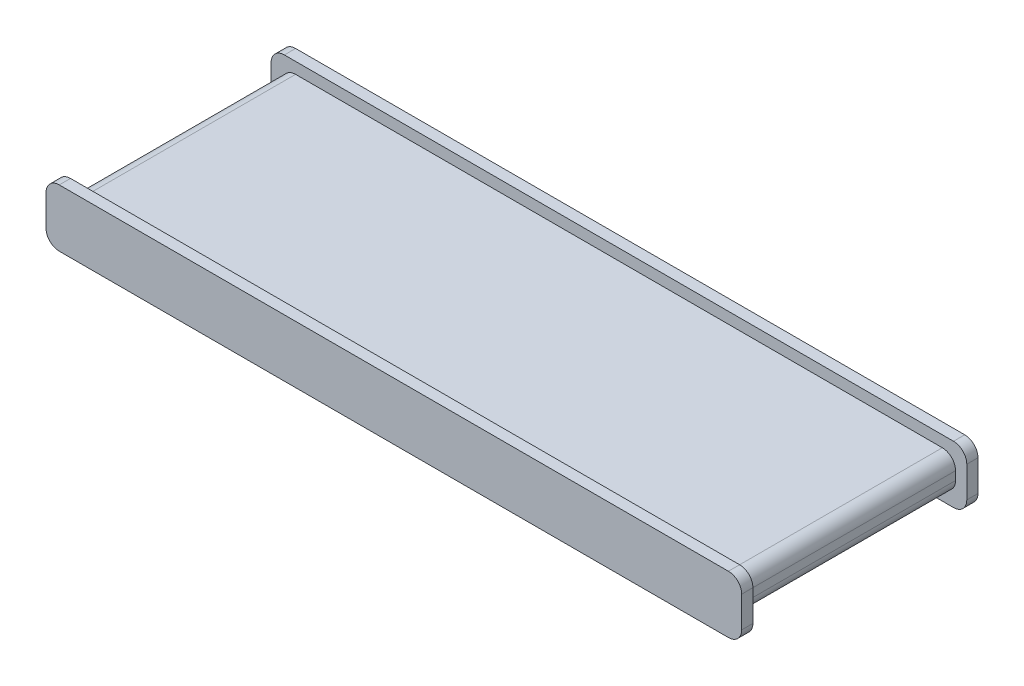
SolidWorks part; units mm, degrees
material "ABS"
ref_plane "X-Y Datum" through (0, 0, 0) normal (0, 0, 1) x (1, 0, 0)
ref_plane "X-Z Datum" through (0, 0, 0) normal (0, 1, 0) x (1, 0, 0)
ref_plane "Y-Z Datum" through (0, 0, 0) normal (1, 0, 0) x (0, 0, -1)
sketch "Sketch2" plane through (0, 0, 0) normal (0, 0, 1) x (1, 0, 0)
  line L6 (152.4, 7.9241) -> (0, 7.9241)
  line L7 (152.4, 7.9241) -> (152.4, 0)
  line L8 (152.4, 0) -> (0, 0)
  line L9 (0, 7.9241) -> (0, 0)
  dimension "D1" = 152.4
extrude "Boss-Extrude1" add sketch "Sketch2" along normal blind 48.42
fillet "Fillet1" radius 3 4 edges at (152.4, 7.9241, 24.21) (152.4, 0, 24.21) (0, 7.9241, 24.21) (0, 0, 24.21)
sketch "Sketch3" plane through (0, 0, 48.42) normal (0, 0, 1) x (1, 0, 0)
  line L0 (149.4, 7.9241) -> (3, 7.9241) construction
  line L1 (-2.54, -2.54) -> (154.94, -2.54)
  line L2 (-2.54, -2.54) -> (-2.54, 10.4641)
  line L3 (-2.54, 10.4641) -> (154.94, 10.4641)
  line L4 (154.94, -2.54) -> (154.94, 10.4641)
  line L5 (3, 0) -> (149.4, 0) construction
  line L6 (0, 4.9241) -> (0, 3) construction
  line L7 (152.4, 3) -> (152.4, 4.9241) construction
  dimension "D1" = 2.54
  dimension "D2" = 2.54
  dimension "D3" = 2.54
  dimension "D4" = 2.54
extrude "Boss-Extrude2" add sketch "Sketch3" along normal blind 2.54
sketch "Sketch4" plane through (0, 0, 0) normal (0, 0, -1) x (-1, 0, 0)
  line L1 (-154.94, 10.4641) -> (2.54, 10.4641)
  line L2 (-154.94, 10.4641) -> (-154.94, -2.54)
  line L3 (-154.94, -2.54) -> (2.54, -2.54)
  line L4 (2.54, 10.4641) -> (2.54, -2.54)
extrude "Boss-Extrude3" add sketch "Sketch4" along normal blind 2.54
fillet "Fillet2" radius 3 8 edges at (-2.54, -2.54, -1.27) (-2.54, 10.4641, -1.27) (154.94, 10.4641, -1.27) (154.94, -2.54, -1.27) (154.94, 10.4641, 49.69) (154.94, -2.54, 49.69) (-2.54, 10.4641, 49.69) (-2.54, -2.54, 49.69)
